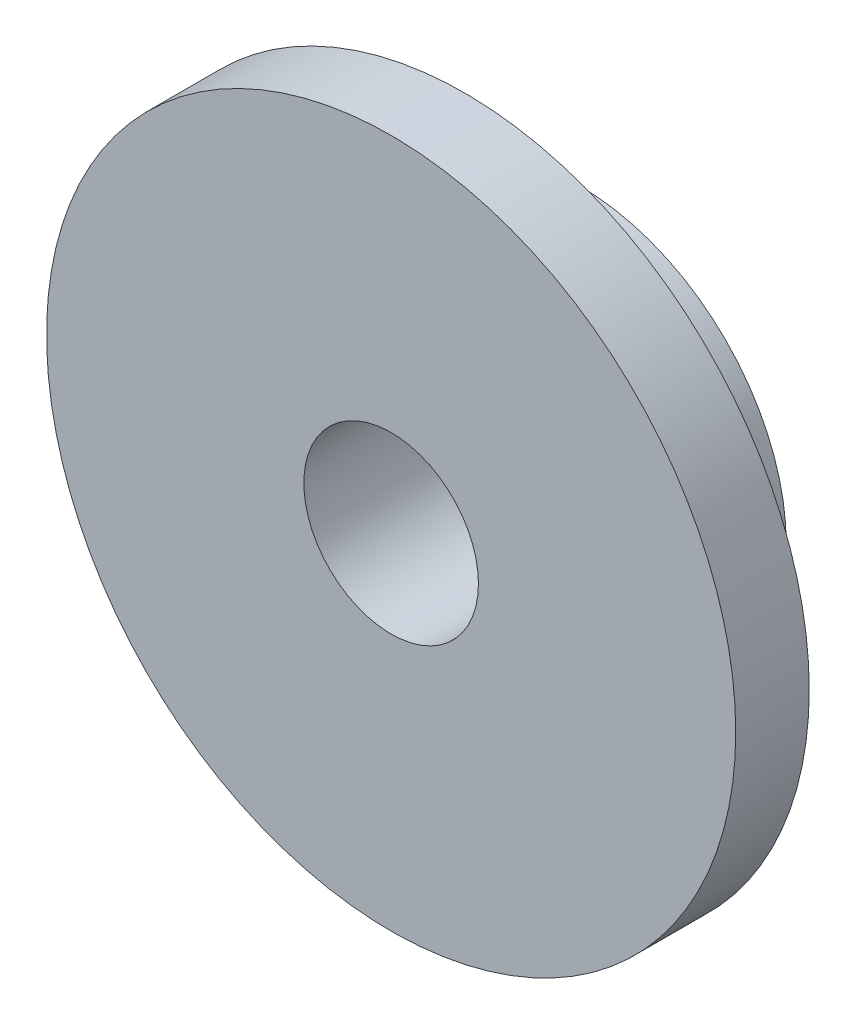
SolidWorks part; units mm, degrees
material "ABS"
ref_plane "正面" through (0, 0, 0) normal (0, 0, 1) x (1, 0, 0)
ref_plane "平面" through (0, 0, 0) normal (0, 1, 0) x (1, 0, 0)
ref_plane "右側面" through (0, 0, 0) normal (1, 0, 0) x (0, 0, -1)
sketch "ｽｹｯﾁ1" plane through (0, 0, 0) normal (0, 0, 1) x (1, 0, 0)
  circle A0 centre (0, 0) radius 1.9
  circle A1 centre (0, 0) radius 4.5
  dimension "D1" = 3.8
  dimension "D2" = 9
extrude "ﾎﾞｽ - 押し出し1" add sketch "ｽｹｯﾁ1" along normal blind 2.5
sketch "ｽｹｯﾁ2" plane through (0, 0, 2.5) normal (0, 0, 1) x (1, 0, 0)
  circle A0 centre (0, 0) radius 1.9
  circle A1 centre (0, 0) radius 7.5
  circle A2 centre (0, 0) radius 1.9 construction
  dimension "D1" = 15
extrude "ﾎﾞｽ - 押し出し2" add sketch "ｽｹｯﾁ2" along normal blind 1.6
